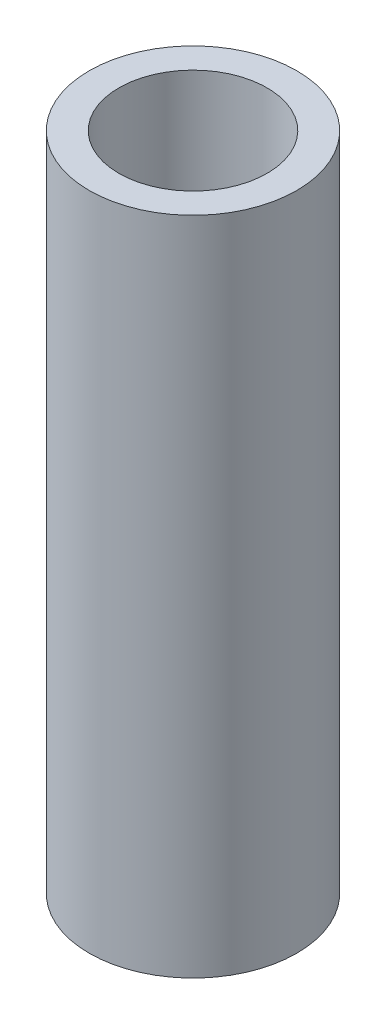
SolidWorks part; units mm, degrees
ref_plane "Front Plane" through (0, 0, 0) normal (0, 0, 1) x (1, 0, 0)
ref_plane "Top Plane" through (0, 0, 0) normal (0, 1, 0) x (1, 0, 0)
ref_plane "Right Plane" through (0, 0, 0) normal (1, 0, 0) x (0, 0, -1)
sketch "Sketch1" plane through (0, 0, 0) normal (0, 1, 0) x (1, 0, 0)
  circle A0 centre (0, 0) radius 1.5875
  circle A1 centre (0, 0) radius 2.2225
  dimension "D1" = 3.175
  dimension "D2" = 4.445
extrude "Boss-Extrude1" add sketch "Sketch1" along normal blind 14.1503
